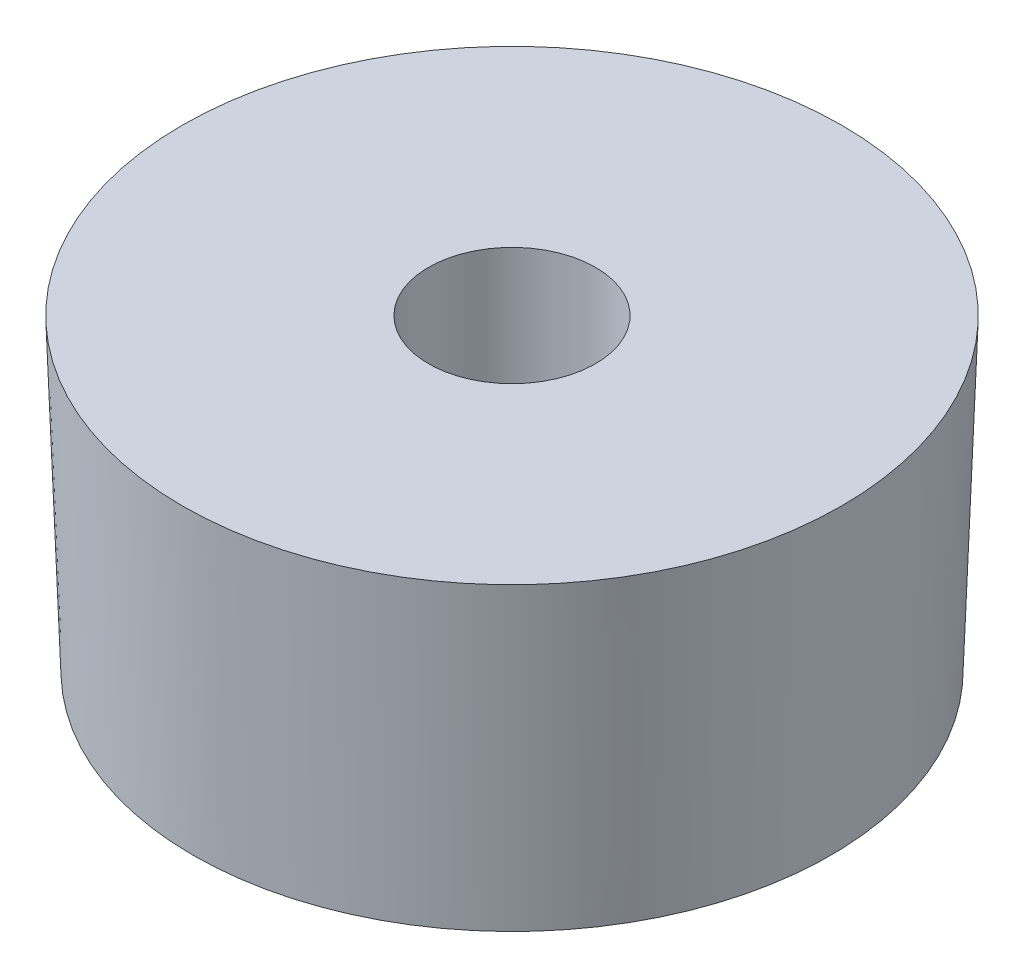
SolidWorks part; units mm, degrees
ref_plane "Front Plane" through (0, 0, 0) normal (0, 0, 1) x (1, 0, 0)
ref_plane "Top Plane" through (0, 0, 0) normal (0, 1, 0) x (1, 0, 0)
ref_plane "Right Plane" through (0, 0, 0) normal (1, 0, 0) x (0, 0, -1)
sketch "Sketch1" plane through (0, 0, 0) normal (0, 1, 0) x (1, 0, 0)
  circle A0 centre (0, 0) radius 7.25
  dimension "D1" = 14.5
extrude "Boss-Extrude2" add sketch "Sketch1" along normal blind 7 draft 2 contours A0 draft outward yes
sketch "Sketch5" plane through (0, 0, 0) normal (0, -1, 0) x (1, 0, 0)
  point P0 (0, 0)
hole_wizard "CBORE for #6 Binding Head Machine Screw1" positions "Sketch6" profile "Sketch7" counterbore size "#6" standard "ANSI Inch" end condition through all
sketch "Sketch6" plane through (0, 0, 0) normal (0, -1, 0) x (-1, 0, 0)
  point P0 (0, 0)
sketch "Sketch7" plane through (0, 0, 0) normal (1, 0, 0) x (0, 0, -1)
  line L0 (0, 0) -> (0, 7)
  line L1 (0, 7) -> (1.8986, 7)
  line L3 (1.8986, 7) -> (1.8986, 2.2098)
  line L4 (1.8986, 2.2098) -> (3.9687, 2.2098)
  line L5 (3.9687, 2.2098) -> (3.9687, 0)
  line L7 (3.9687, 0) -> (0, 0)
  line L11 (0, -6.35) -> (0, 107.95) construction
  dimension "Thru Hole Dia." = 3.7973
  dimension "Thru Hole Depth" = 7
  dimension "C'Bore Dia." = 7.9375
  dimension "C'Bore Depth" = 2.2098
